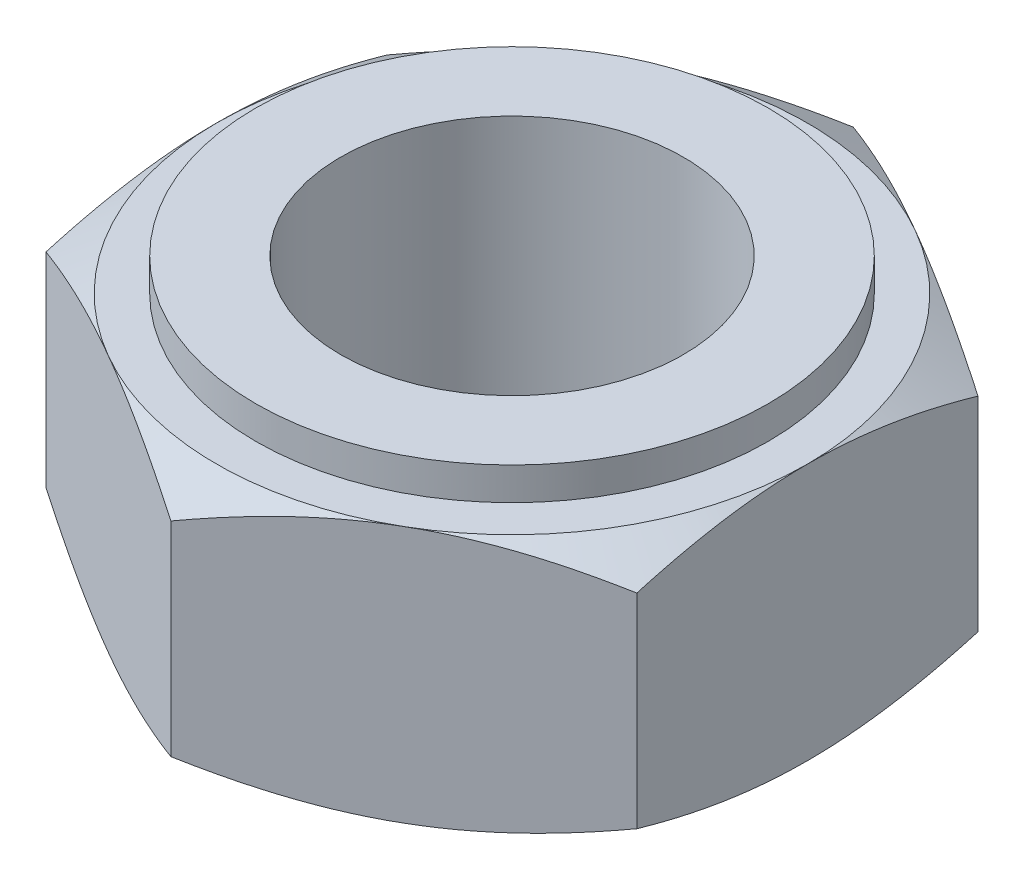
SolidWorks part; units mm, degrees
ref_plane "Front Plane" through (0, 0, 0) normal (0, 0, 1) x (1, 0, 0)
ref_plane "Top Plane" through (0, 0, 0) normal (0, 1, 0) x (1, 0, 0)
ref_plane "Right Plane" through (0, 0, 0) normal (1, 0, 0) x (0, 0, -1)
sketch "Sketch1" plane through (0, 0, 0) normal (0, 1, 0) x (1, 0, 0)
  line L1 (-3.45, 1.9919) -> (-3.45, -1.9919)
  line L2 (-3.45, -1.9919) -> (0, -3.9837)
  line L3 (0, -3.9837) -> (3.45, -1.9919)
  line L4 (3.45, -1.9919) -> (3.45, 1.9919)
  line L5 (3.45, 1.9919) -> (0, 3.9837)
  line L6 (0, 3.9837) -> (-3.45, 1.9919)
  circle A0 centre (0, 0) radius 3.45 construction
  circle A1 centre (0, 0) radius 2
  dimension "Thread Size" = 4
  dimension "Hex" = 6.9
extrude "Boss-Extrude1" add sketch "Sketch1" along normal mid plane 3
sketch "Sketch2" plane through (0, 1.5, 0) normal (0, 1, 0) x (1, 0, 0)
  circle A0 centre (0, 0) radius 2 construction
  circle A1 centre (0, 0) radius 2
curve "Helix/Spiral1" pitch 0.7 height 3.7 turns 5.2857 parameters "Pitch"=0.7
sketch "Sketch6" plane through (0, 1.5, 0) normal (0, 1, 0) x (1, 0, 0)
  line L0 (0, -2) -> (0, -3.9837) construction
  circle A0 centre (0, 0) radius 2 construction
  circle A1 centre (0, 0) radius 2
  circle A2 centre (0, 0) radius 2.9919
  point P7 (0, -2.9919)
extrude "Boss-Extrude2" add sketch "Sketch6" along normal blind 0.381
sketch "Sketch5" plane through (0, 1.5, 0) normal (0, 1, 0) x (1, 0, 0)
  circle A0 centre (0, 0) radius 3.45 construction
  circle A1 centre (0, 0) radius 3.45
extrude "Cut-Extrude2" cut sketch "Sketch5" against normal through all draft 60 flip side to cut
mirror "Mirror2" about plane through (0, 0, 0) normal (0, 1, 0) of "Cut-Extrude2"
sketch "Sketch3" [suppressed] plane through (0, 0, 0) normal (1, 0, 0) x (0, 0, -1)
  line L0 (1.5453, 1.85) -> (2, 2.1125)
  line L1 (2, 2.1125) -> (2, 1.5)
  line L2 (2, 1.5) -> (1.5453, 1.7625)
  line L3 (1.5453, 1.7625) -> (1.5453, 1.85)
  line L4 (1.7727, 1.9813) -> (1.7727, 1.6313) construction
  line L5 (1.5453, 1.8063) -> (2, 1.8063) construction
  line L6 (2, 1.5) -> (-2, 1.5) construction
  dimension "D1" = 60
  dimension "D2" = 0.0875
  dimension "D3" = 0.35
sweep "Sweep1" [suppressed] add profiles "Sketch3" path "Helix/Spiral1"
sketch "Sketch4" [suppressed] plane through (0, 1.5, 0) normal (0, 1, 0) x (1, 0, 0)
  circle A1 centre (0, 0) radius 2
  circle A2 centre (0, 0) radius 2
  dimension "D1" = 0
extrude "Cut-Extrude1" [suppressed] cut sketch "Sketch4" along normal through all and the other way through all draft 45
mirror "Mirror1" [suppressed] about plane through (0, 0, 0) normal (0, 1, 0)
ref_axis "Center Axis 1" through (0, 1.5, 0) along (0, -1, 0)
ref_plane "Contact Plane 1" through (0, 1.881, 0) normal (0, 1, 0) x (1, 0, 0)
ref_plane "Contact Plane 2" through (0, 1.5, 0) normal (0, 1, 0) x (1, 0, 0)
ref_plane "Contact Plane 3" through (0, -1.5, 0) normal (0, -1, 0) x (-1, 0, 0)
equation "\"D2@Sketch3\" = \"Pitch@Helix/Spiral1\"*.125"
equation "\"D3@Sketch3\" = \"Pitch@Helix/Spiral1\"*.5"
equation "\"D3@Helix/Spiral1\" = \"Height@Boss-Extrude1\"+\"Pitch@Helix/Spiral1\""
